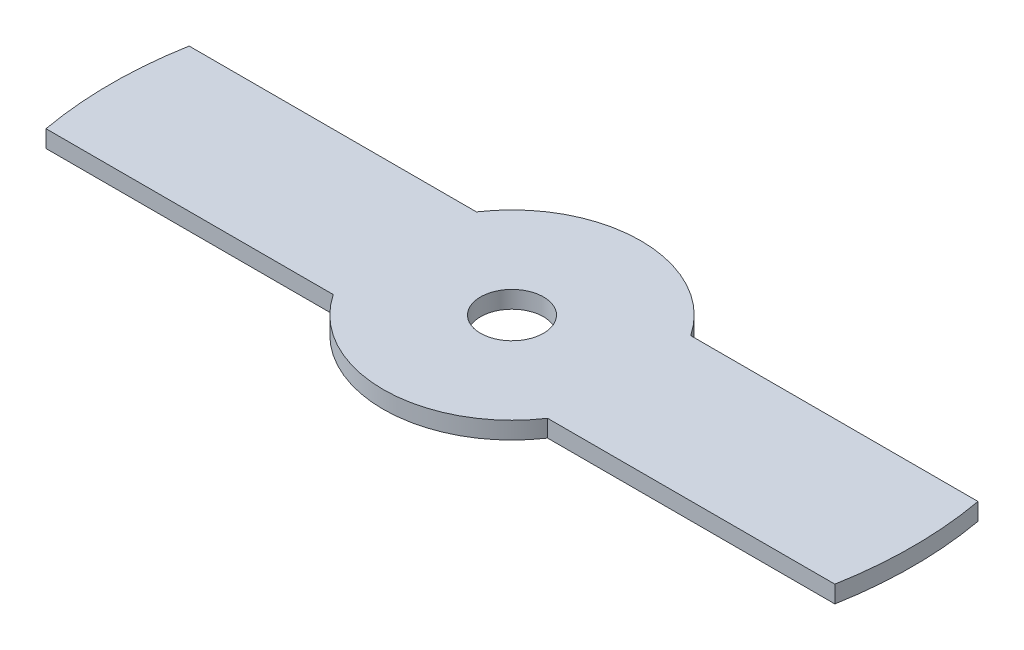
SolidWorks part; units mm, degrees
ref_plane "Alzado" through (0, 0, 0) normal (0, 0, 1) x (1, 0, 0)
ref_plane "Planta" through (0, 0, 0) normal (0, 1, 0) x (1, 0, 0)
ref_plane "Vista lateral" through (0, 0, 0) normal (1, 0, 0) x (0, 0, -1)
sketch "Croquis1" plane through (0, 0, 0) normal (0, 1, 0) x (1, 0, 0)
  line L19 (-18.7083, 12.5) -> (-68.8749, 12.5)
  line L28 (18.7083, 12.5) -> (68.8749, 12.5)
  line L30 (18.7083, -12.5) -> (68.8749, -12.5)
  line L31 (-18.7083, -12.5) -> (-68.8749, -12.5)
  circle A0 centre (0, 0) radius 5.5
  arc A2 (-68.8749, 12.5) -> (-68.8749, -12.5) centre (0, 0) ccw
  arc A4 (-18.7083, -12.5) -> (18.7083, -12.5) centre (0, 0) ccw
  arc A5 (18.7083, 12.5) -> (-18.7083, 12.5) centre (0, 0) ccw
  arc A6 (68.8749, -12.5) -> (68.8749, 12.5) centre (0, 0) ccw
  point P26 (0, 0)
  point P47 (0, 0)
  point P88 (0, 0)
  point P92 (0, 0)
extrude "Saliente-Extruir1" add sketch "Croquis1" along normal blind 3
